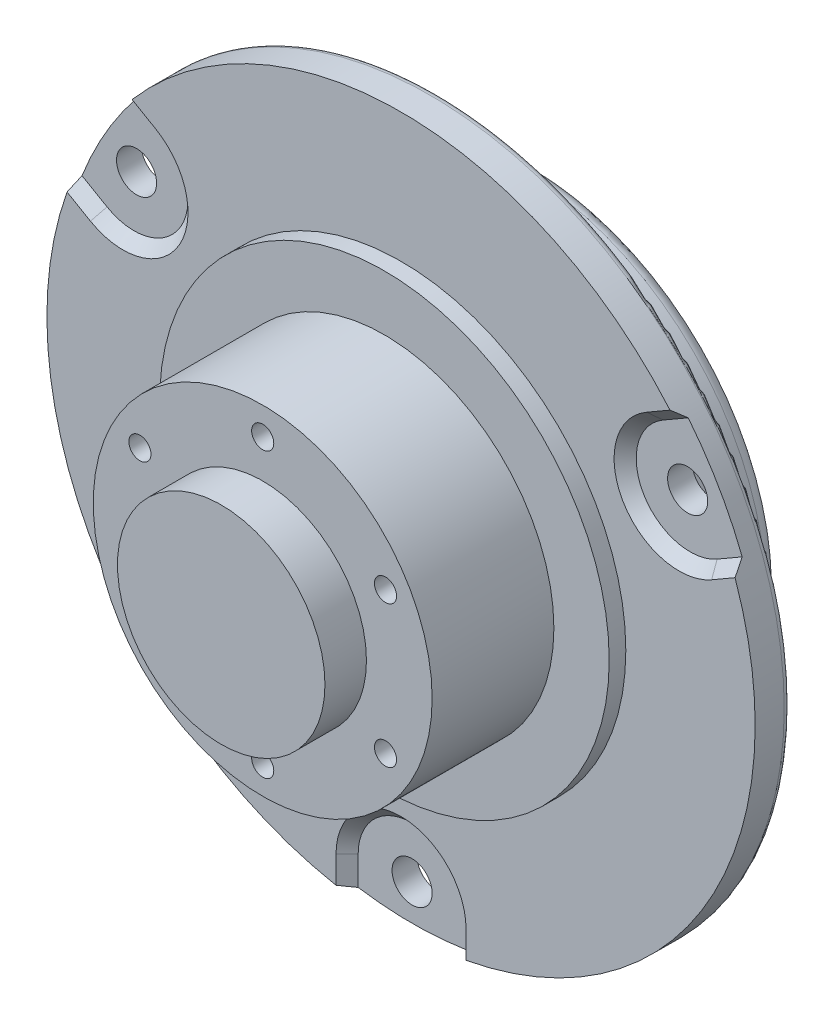
SolidWorks part; units mm, degrees
ref_plane "Front Plane" through (0, 0, 0) normal (0, 0, 1) x (1, 0, 0)
ref_plane "Top Plane" through (0, 0, 0) normal (0, 1, 0) x (1, 0, 0)
ref_plane "Right Plane" through (0, 0, 0) normal (1, 0, 0) x (0, 0, -1)
sketch "Sketch4" plane through (0, 0, 0) normal (0, 0, 1) x (1, 0, 0)
  circle A0 centre (0, 0) radius 25.6
extrude "Boss-Extrude5" add sketch "Sketch4" along normal blind 2.6 contours A0
ref_axis "Axis2" through (0, 0, 24.3732) along (0, 0, -1)
sketch "Sketch5" plane through (0, 0, 2.6) normal (0, 0, 1) x (1, 0, 0)
  circle A0 centre (0, 0) radius 16.25
extrude "Boss-Extrude6" add sketch "Sketch5" along normal blind 1.2
sketch "Sketch6" plane through (0, 0, 3.8) normal (0, 0, 1) x (1, 0, 0)
  circle A0 centre (0, 0) radius 12.25
extrude "Boss-Extrude7" add sketch "Sketch6" along normal blind 8.8
sketch "Sketch7" plane through (0, 0, 12.6) normal (0, 0, 1) x (1, 0, 0)
  circle A0 centre (0, 0) radius 7.5
extrude "Boss-Extrude8" add sketch "Sketch7" along normal blind 3
fillet "Fillet2" radius 0.5 1 edges at (25.6, 0, 0)
sketch "Sketch8" plane through (0, 0, 2.6) normal (0, 0, 1) x (1, 0, 0)
  line L0 (0, -23.2104) -> (0, -30.7896) construction
  line L1 (3.9, -23.2104) -> (3.9, -30.7896)
  line L2 (-3.9, -23.2104) -> (-3.9, -30.7896)
  arc A0 (3.9, -23.2104) -> (-3.9, -23.2104) centre (0, -23.2104) ccw
  arc A1 (-3.9, -30.7896) -> (3.9, -30.7896) centre (0, -30.7896) ccw
  point P2 (0, -27)
extrude "Cut-Extrude1" cut sketch "Sketch8" against normal blind 0.8
chamfer "Chamfer2" distance 0.8 angle 45 3 edges at (-3.9, -24.2558, 2.6) (0, -19.3104, 2.6) (3.9, -24.2558, 2.6)
hole_wizard "M2.5 Clearance Hole1" positions "Sketch9" profile "Sketch10" hole size "M2.5" standard "ANSI Metric" end condition through all
sketch "Sketch9" plane through (0, 0, 1.8) normal (0, 0, 1) x (1, 0, 0)
  point P0 (0, -23)
  point P3 (0, 0)
sketch "Sketch10" plane through (0, -23, 1.8) normal (1, 0, 0) x (0, -1, 0)
  line L0 (0, 0) -> (0, 1.8)
  line L1 (0, 1.8) -> (1.45, 1.8)
  line L2 (1.45, 1.8) -> (1.45, 0)
  line L5 (1.45, 0) -> (0, 0)
  line L11 (0, -6.35) -> (0, 107.95) construction
  dimension "Thru Hole Dia." = 2.9
  dimension "Thru Hole Depth" = 1.8
pattern_circular "CirPattern1" count 3 over 360 about axis through (0, 0, 24.3732) along (0, 0, -1) of "Cut-Extrude1", "M2.5 Clearance Hole1", "Chamfer2"
hole_wizard "Tap Drill for M2x0.4 Tap1" positions "Sketch11" profile "Sketch12" hole size "M2x0.4" standard "ANSI Metric"
sketch "Sketch11" plane through (0, 0, 12.6) normal (0, 0, 1) x (1, 0, 0)
  point P0 (0, -10.25)
  point P3 (0, 0)
  point P4 (0, 0)
sketch "Sketch12" plane through (0, -10.25, 12.6) normal (1, 0, 0) x (0, -1, 0)
  line L0 (0, 0) -> (0, 6.4807)
  line L1 (0, 6.4807) -> (0.8, 6)
  line L2 (0.8, 6) -> (0.8, 0)
  line L5 (0.8, 0) -> (0, 0)
  line L10 (0, 6.4807) -> (-0.8, 6) construction
  line L11 (0, -6.35) -> (0, 107.95) construction
  dimension "Hole Dia." = 1.6
  dimension "Hole Depth" = 6
  dimension "Drill Angle" = 118
pattern_circular "CirPattern2" count 6 over 360 about axis through (0, 0, 24.3732) along (0, 0, -1) of "Tap Drill for M2x0.4 Tap1"
sketch "Sketch13" plane through (0, 0, 0) normal (0, 0, -1) x (-1, 0, 0)
  circle A0 centre (0, 0) radius 18.75
extrude "Boss-Extrude9" add sketch "Sketch13" along normal blind 2
sketch "Sketch14" plane through (0, 0, -2) normal (0, 0, -1) x (-1, 0, 0)
  circle A0 centre (0, 0) radius 17.75
  point P2 (-4.2273, 11.4437)
extrude "Boss-Extrude10" add sketch "Sketch14" along normal blind 5
sketch "Sketch17" plane through (0, 0, -7) normal (0, 0, -1) x (-1, 0, 0)
  line L0 (4.9497, -4.9497) -> (0, 0) construction
  line L3 (-0.2816, -7.2816) -> (-2.1213, -9.1213)
  line L4 (7.2816, 0.2816) -> (9.1213, 2.1213)
  line L5 (11.9497, 2.1213) -> (17.4294, -3.3583)
  line L6 (-2.1213, -11.9497) -> (3.3583, -17.4294)
  arc A0 (0.3723, -6.9901) -> (6.9901, -0.3723) centre (0, 0) ccw
  circle A1 centre (0, 0) radius 17.75 construction
  arc A3 (3.3583, -17.4294) -> (17.4294, -3.3583) centre (0, 0) ccw
  arc A4 (9.1213, 2.1213) -> (11.9497, 2.1213) centre (10.5355, 0.7071) cw
  arc A5 (-2.1213, -9.1213) -> (-2.1213, -11.9497) centre (-0.7071, -10.5355) ccw
  arc A6 (0.3723, -6.9901) -> (-0.2816, -7.2816) centre (0.4255, -7.9887) ccw
  arc A7 (6.9901, -0.3723) -> (7.2816, 0.2816) centre (7.9887, -0.4255) cw
  point P9 (0, 0)
  dimension "D1" = 2
  dimension "D2" = 1
  dimension "D3" = 1
extrude "Cut-Extrude3" cut sketch "Sketch17" against normal blind 1.8
fillet "Fillet6" radius 2 2 edges at (-3.3583, -17.4294, -6.1) (-17.4294, -3.3583, -6.1)
fillet "Fillet8" radius 1 12 edges at (-10.5355, 2.7071, -7) (-8.2014, 1.2014, -7) (-7.0753, -0.0184, -7) (-4.9497, -4.9497, -7) (-0.0184, -7.0753, -7) (1.2014, -8.2014, -7) (2.7071, -10.5355, -7) (0.951, -13.1201, -7) (-0.6225, -16.5396, -7) (12.5511, 12.5511, -7) (-13.1201, 0.951, -7) (-16.5396, -0.6225, -7)
